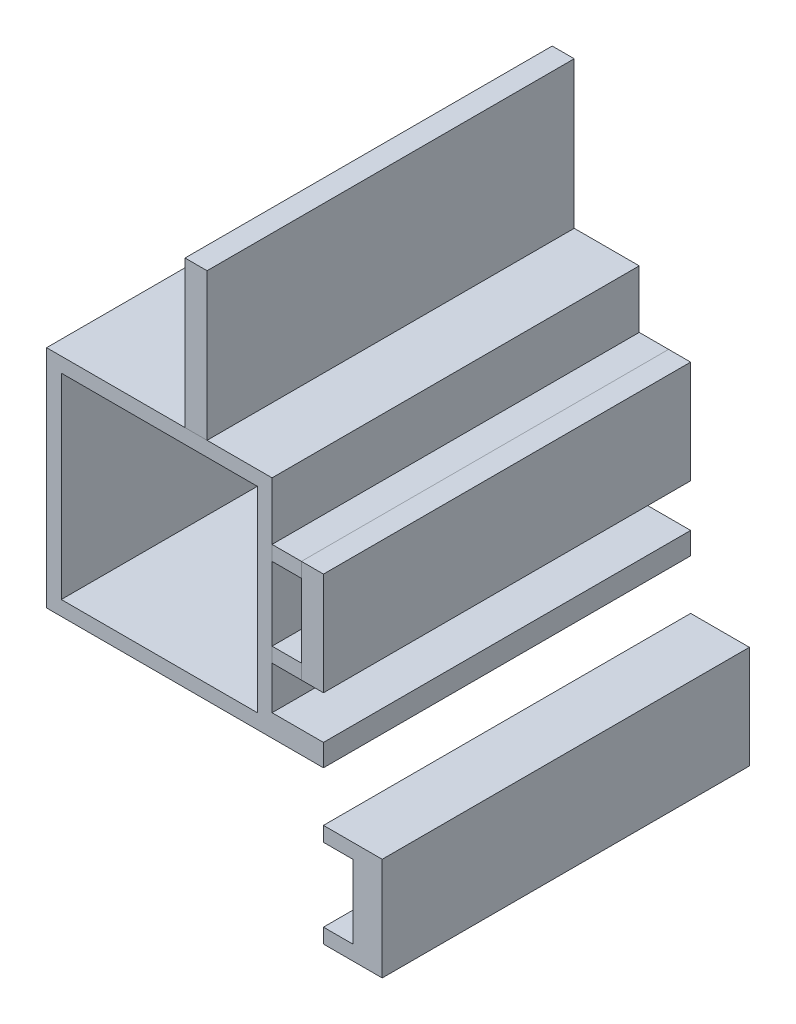
SolidWorks part; units mm, degrees
ref_plane "Alzado" through (0, 0, 0) normal (0, 0, 1) x (1, 0, 0)
ref_plane "Planta" through (0, 0, 0) normal (0, 1, 0) x (1, 0, 0)
ref_plane "Vista lateral" through (0, 0, 0) normal (1, 0, 0) x (0, 0, -1)
sketch "Croquis2" plane through (0, 0, 0) normal (0, 0, 1) x (1, 0, 0)
  line L0 (-51.9511, -1.694) -> (-49.9511, -1.694)
  line L1 (-49.9511, -1.694) -> (-51.9511, -1.694)
  line L2 (-1.9511, -10.694) -> (-1.9511, -41.694)
  line L3 (-1.9511, -41.694) -> (-51.9511, -41.694) construction
  line L4 (-51.9511, -1.694) -> (-51.9511, -41.694) construction
  line L5 (-49.9511, -1.694) -> (-49.9511, -11.294)
  line L6 (-49.9511, -11.294) -> (-36.9511, -11.294)
  line L7 (-36.9511, -11.294) -> (-36.9511, -9.294)
  line L8 (-36.9511, -9.294) -> (-31.9511, -9.294)
  line L9 (-31.9511, -9.294) -> (-31.9511, -11.994)
  line L10 (-31.9511, -11.994) -> (-17.3111, -11.994)
  line L11 (-17.3111, -11.994) -> (-17.3111, -7.694)
  line L12 (-17.3111, -7.694) -> (-24.3111, -7.694)
  line L13 (-24.3111, -7.694) -> (-24.3111, -4.694)
  line L14 (-24.3111, -4.694) -> (-14.3111, -4.694)
  line L15 (-14.3111, -4.694) -> (-14.3111, -10.694)
  line L16 (-14.3111, -10.694) -> (-1.9511, -10.694)
  line L17 (-1.9511, -41.694) -> (-4.5642, -41.694)
  line L18 (-4.5642, -41.694) -> (-4.5642, -19.454)
  line L19 (-4.5642, -19.454) -> (-22.3242, -19.454) construction
  line L20 (-22.3242, -41.694) -> (-22.3242, -15.394) construction
  line L21 (-4.5642, -19.454) -> (-22.3242, -15.394)
  line L22 (-42.1842, -30.694) -> (-40.1642, -30.694)
  line L23 (-22.3242, -15.394) -> (-26.7442, -15.394) construction
  line L24 (-42.1842, -41.694) -> (-42.1842, -30.694) construction
  line L25 (-40.1642, -41.694) -> (-40.1642, -30.694) construction
  line L26 (-26.7442, -15.394) -> (-26.7442, -15.354)
  line L27 (-22.3242, -15.394) -> (-26.7442, -15.354)
  line L28 (-40.1642, -30.694) -> (-26.7442, -15.354) construction
  arc A0 (-40.1642, -30.694) -> (-26.7442, -15.354) centre (-26.4173, -29.1801) cw
  dimension "D1" = 2
  dimension "D2" = 50
  dimension "D3" = 40
  dimension "D4" = 9.6
  dimension "D5" = 13
  dimension "D6" = 2
  dimension "D7" = 5
  dimension "D8" = 2.7
  dimension "D9" = 14.64
  dimension "D10" = 4.3
  dimension "D11" = 3
  dimension "D12" = 10
  dimension "D13" = 6
  dimension "D14" = 12.36
  dimension "D15" = 22.24
  dimension "D16" = 17.76
  dimension "D17" = 26.3
  dimension "D18" = 35.6
  dimension "D19" = 2.02
  dimension "D20" = 11
  dimension "D21" = 4.42
  dimension "D22" = 0.04
sketch "Croquis3" plane through (0, 0, 0) normal (0, 0, 1) x (1, 0, 0)
  line L114 (-15.1572, 8.4809) -> (-41.8572, 8.4809)
  line L133 (-13.1572, 9.4809) -> (-13.1572, 35.1809)
  line L147 (-27.0072, 35.1809) -> (-27.0072, 37.1809) construction
  line L167 (-43.8572, 37.1809) -> (-27.0072, 37.1809)
  line L182 (-15.1572, 35.1809) -> (-41.8572, 35.1809)
  line L183 (-41.8572, 8.4809) -> (-41.8572, 35.1809)
  line L184 (-15.1572, 8.4809) -> (-15.1572, 35.1809)
  line L190 (-43.8572, 37.1809) -> (-43.8572, 6.4809)
  line L192 (-13.1572, 35.1809) -> (-9.1572, 35.1809)
  line L193 (-9.1572, 35.1809) -> (-9.1572, 9.4809)
  line L194 (-9.1572, 9.4809) -> (-13.1572, 9.4809)
  line L195 (-9.1572, 22.3309) -> (-6.1572, 22.3309) construction
  line L196 (-27.0072, 37.1809) -> (-6.1572, 37.1809)
  line L202 (-43.8572, 6.4809) -> (-6.1572, 6.4809)
  line L214 (-6.1572, 6.4809) -> (-6.1572, 37.1809)
  dimension "D5" = 26.7
  dimension "D13" = 3
  dimension "D3" = 2
  dimension "D10" = 37.7
  dimension "D4" = 26.7
  dimension "D8" = 4
  dimension "D12" = 2
  dimension "D28" = 16.85
extrude "Saliente-Extruir1" add sketch "Croquis3" along normal blind 50 contours L196 L214 L202 L190 L167 | L183 L182 L184 L114 | L194 L133 L192 L193
sketch "Croquis11" plane through (0, 0, 0) normal (0, 0, -1) x (-1, 0, 0)
  line L2 (-1.8428, -14.3028) -> (-1.8428, -0.3028)
  line L3 (-1.8428, -0.3028) -> (6.1572, -0.3028)
  line L4 (6.1572, -0.3028) -> (6.1572, -2.3028)
  line L5 (6.1572, -2.3028) -> (2.1572, -2.3028)
  line L6 (2.1572, -2.3028) -> (2.1572, -12.3028)
  line L7 (2.1572, -12.3028) -> (6.1572, -12.3028)
  line L8 (6.1572, -12.3028) -> (6.1572, -14.3028)
  line L9 (-1.8428, -14.3028) -> (6.1572, -14.3028)
  line L14 (2.1572, -7.3028) -> (3.8938, -7.3028) construction
  dimension "D1" = 8
  dimension "D2" = 2
  dimension "D3" = 2
  dimension "D4" = 14
  dimension "D5" = 4
extrude "Saliente-Extruir2" add sketch "Croquis11" along direction (0, 0, 1) on the side against the normal up to surface (50 mm away) contours L9 L8 L7 L6 L5 L4 L3 L2 up to face at (-11.1572, 22.3309, 50)
sketch "Croquis12" plane through (1.8428, 0, 0) normal (1, 0, 0) x (0, 0, -1)
  line L0 (-45.4229, -7.3028) -> (-43.4878, -7.3028) construction
  line L2 (0, -7.3028) -> (-1.743, -7.3028) construction
  line L4 (0, -0.3028) -> (0, -14.3028) construction
  line L5 (-25, -9.8028) -> (-4.8, -9.8028)
  line L8 (-4.8, -4.8028) -> (-45.4229, -4.8028)
  line L9 (-45.4229, -4.8028) -> (-45.4229, -9.8028)
  line L10 (-45.4229, -9.8028) -> (-25, -9.8028)
  line L11 (-4.8, -9.8028) -> (-4.8, -4.8028)
  dimension "D3" = 5
extrude "Cortar-Extruir12" cut sketch "Croquis12" against normal up to surface (10 mm away) contours L11 L8 L9 L10 L5 rebuild error yes
fillet "Redondeo1" radius 2.5 rebuild error yes
sketch "Croquis14" plane through (-6.1572, 0, 0) normal (1, 0, 0) x (0, 0, -1)
  line L1 (-50, 9.4809) -> (-50, 35.1809) construction
  line L2 (-50, 22.3309) -> (-47.0206, 22.3309) construction
  line L3 (-25, 37.1809) -> (-25, 24.8309) construction
  line L6 (-47.0206, 22.3309) -> (-47.0206, 24.8309)
  line L7 (-47.0206, 24.8309) -> (-2.9794, 24.8309)
  line L8 (-47.0206, 22.3309) -> (-47.0206, 19.8309)
  line L9 (-47.0206, 19.8309) -> (-2.9794, 19.8309)
  line L10 (-2.9794, 22.3309) -> (-2.9794, 19.8309)
  line L11 (-2.9794, 22.3309) -> (-2.9794, 24.8309)
  point P12 (-25, 19.8309)
  dimension "D1" = 2.5
  dimension "D2" = 2.5
extrude "Cortar-Extruir14" cut sketch "Croquis14" against normal up to surface (9 mm away) contours L10 L11 L7 L6 L8 L9 rebuild error yes up to face at (-15.1572, 21.8309, 25)
fillet "Redondeo2" radius 2.5 rebuild error yes
fillet "Redondeo4" radius 2.5 rebuild error yes
ref_plane "Plano1" through (-48.1572, 0, 0) normal (-1, 0, 0) x (0, 0, 1)
sketch "Croquis16" plane through (-48.1572, 0, 0) normal (-1, 0, 0) x (0, 0, 1)
  line L0 (32, -25.4812) -> (18, -25.4812)
  line L2 (25, 5.245) -> (25, 1.245) construction
  line L3 (50, 5.245) -> (0, 5.245) construction
  line L9 (5, -11.755) -> (5, -12.4812)
  line L10 (32, 1.245) -> (18, 1.245)
  line L11 (45, -12.4812) -> (45, -11.755)
  line L16 (5, -12.1181) -> (45, -12.1181) construction
  arc A0 (32, 1.245) -> (45, -11.755) centre (32, -11.755) cw
  arc A3 (5, -11.755) -> (18, 1.245) centre (18, -11.755) cw
  arc A4 (32, -25.4812) -> (45, -12.4812) centre (32, -12.4812) ccw
  arc A5 (5, -12.4812) -> (18, -25.4812) centre (18, -12.4812) ccw
  point P0 (25, 5.245)
  dimension "D2" = 7
  dimension "D1" = 4
extrude "Cortar-Extruir17" cut sketch "Croquis16" against normal up to surface (16.5053 mm away) rebuild error yes
sketch "Croquis17" plane through (-43.8572, 0, 0) normal (-1, 0, 0) x (0, 0, 1)
  line L0 (25, 32.1809) -> (25, 37.1809) construction
  line L1 (3, 12.4809) -> (47, 12.4809)
  line L2 (3, 12.4809) -> (3, 32.1809)
  line L3 (3, 32.1809) -> (47, 32.1809)
  line L4 (47, 12.4809) -> (47, 32.1809)
  line L5 (50, 37.1809) -> (0, 37.1809) construction
  line L6 (47, 22.3309) -> (50, 22.3309) construction
  line L7 (50, 37.1809) -> (50, 6.4809) construction
  line L8 (3, 22.3309) -> (0, 22.3309) construction
  line L9 (0, 37.1809) -> (0, 6.4809) construction
  line L12 (50, 7.4809) -> (0, 7.4809) construction
  dimension "D1" = 3
  dimension "D2" = 3
  dimension "D3" = 5
  dimension "D4" = 5
extrude "Cortar-Extruir18" cut sketch "Croquis17" against normal up to next contours L1 L4 L3 L2 rebuild error yes
fillet "Redondeo5" radius 10 rebuild error yes
sketch "Croquis18" plane through (0, 37.1809, 0) normal (0, 1, 0) x (1, 0, 0)
  line L0 (-28.5072, -4) -> (-28.5072, 0) construction
  line L1 (-25.0072, -46) -> (-32.0072, -46)
  line L2 (-25.0072, -46) -> (-25.0072, -4)
  line L3 (-25.0072, -4) -> (-32.0072, -4)
  line L4 (-15.1572, 0) -> (-41.8572, 0)
  line L5 (-15.1572, -50) -> (-15.1572, 0)
  line L6 (-41.8572, -50) -> (-15.1572, -50)
  line L7 (-41.8572, 0) -> (-41.8572, -50)
  line L8 (-15.1572, 0) -> (-41.8572, 0) construction
  line L9 (-15.1572, -50) -> (-15.1572, 0) construction
  line L10 (-41.8572, -50) -> (-15.1572, -50) construction
  line L11 (-41.8572, 0) -> (-41.8572, -50) construction
  line L12 (-32.0072, -46) -> (-32.0072, -4)
  point P8 (-28.5072, -4)
  point P9 (-28.5072, 0)
  dimension "D2" = 4
  dimension "D3" = 4
  dimension "D4" = 7
  dimension "D1" = 0
extrude "Cortar-Extruir19" cut sketch "Croquis18" against normal up to next rebuild error yes
sketch "Croquis19" plane through (0, 0, 0) normal (0, 0, -1) x (-1, 0, 0)
  line L0 (9.1572, 35.1809) -> (9.1572, 9.4809) construction
  line L1 (9.1572, 17.3309) -> (13.1572, 17.3309)
  line L2 (9.1572, 17.3309) -> (9.1572, 15.3309)
  line L3 (9.1572, 15.3309) -> (13.1572, 15.3309)
  line L4 (13.1572, 17.3309) -> (13.1572, 15.3309)
  line L5 (13.1572, 9.4809) -> (13.1572, 35.1809) construction
  line L6 (9.1572, 17.3309) -> (9.1572, 22.3309) construction
  line L7 (9.1572, 22.3309) -> (7.709, 22.3309) construction
  line L8 (13.1572, 27.3309) -> (13.1572, 29.3309)
  line L9 (9.1572, 29.3309) -> (13.1572, 29.3309)
  line L10 (9.1572, 27.3309) -> (9.1572, 29.3309)
  line L11 (9.1572, 27.3309) -> (13.1572, 27.3309)
  line L12 (25.0072, 37.1809) -> (32.0072, 37.1809) construction
  line L13 (25.0072, 37.1809) -> (32.0072, 37.1809) construction
  line L15 (25.0072, 37.1809) -> (22.0072, 37.1809)
  line L16 (25.0072, 37.1809) -> (25.0072, 57.1809)
  line L17 (25.0072, 57.1809) -> (22.0072, 57.1809)
  line L18 (22.0072, 37.1809) -> (22.0072, 57.1809)
  dimension "D1" = 2
  dimension "D2" = 5
  dimension "D3" = 3
  dimension "D4" = 20
extrude "Saliente-Extruir3" add sketch "Croquis19" against normal up to surface (50 mm away) up to face at (-11.1572, 22.3309, 50)
sketch "Croquis20" plane through (-25.0072, 0, 0) normal (-1, 0, 0) x (0, 0, 1)
  line L0 (0, 46.1809) -> (20.5, 46.1809) construction
  line L1 (0, 37.1809) -> (0, 57.1809) construction
  line L2 (20.5, 46.1809) -> (30, 46.1809) construction
  line L3 (30, 46.1809) -> (30, 37.1809) construction
  line L4 (25.25, 46.1809) -> (25.25, 35.1809) construction
  line L5 (3, 44.3809) -> (3, 47.9809)
  line L6 (3, 47.9809) -> (47, 47.9809)
  line L7 (47, 47.9809) -> (47, 44.3809)
  line L8 (50, 57.1809) -> (50, 37.1809) construction
  line L9 (3, 44.3809) -> (47, 44.3809)
  line L10 (30, 37.1809) -> (4, 37.1809) construction
  line L11 (47, 47.9809) -> (47, 50.9809) construction
  line L14 (47, 44.3809) -> (47, 37.1809) construction
  line L15 (46, 35.1809) -> (4, 35.1809) construction
  point P15 (47, 46.1809)
  point P16 (3, 46.1809)
  dimension "D1" = 20.5
  dimension "D2" = 9.5
  dimension "D3" = 3
  dimension "D4" = 3
  dimension "D5" = 3
  dimension "D6" = 1.8
  dimension "D7" = 11
extrude "Cortar-Extruir20" cut sketch "Croquis20" against normal up to next rebuild error yes
sketch "Croquis21" plane through (0, 0, 0) normal (0, 0, -1) x (-1, 0, 0)
  line L0 (13.1572, 35.1809) -> (13.1572, 37.1809)
  line L1 (43.8572, 37.1809) -> (6.1572, 37.1809) construction
  line L2 (13.1572, 37.1809) -> (6.1572, 37.1809)
  line L3 (6.1572, 37.1809) -> (6.1572, 29.3309)
  line L4 (6.1572, 37.1809) -> (6.1572, -0.3028) construction
  line L5 (6.1572, 29.3309) -> (9.1572, 29.3309)
  line L6 (9.1572, 29.3309) -> (9.1572, 35.1809)
  line L7 (9.1572, 35.1809) -> (13.1572, 35.1809)
  line L8 (9.1572, 9.4809) -> (6.1572, 9.4809)
  line L9 (6.1572, 9.4809) -> (6.1572, 15.3309)
  line L10 (6.1572, 15.3309) -> (9.1572, 15.3309)
  line L11 (9.1572, 15.3309) -> (9.1572, 9.4809)
extrude "Cortar-Extruir21" cut sketch "Croquis21" against normal up to next (50 mm away)
fillet "Redondeo6" radius 3 rebuild error yes
fillet "Redondeo8" radius 7 rebuild error yes
fillet "Redondeo9" radius 1.3 rebuild error yes
sketch "Croquis22" plane through (0, 37.1809, 0) normal (0, 1, 0) x (1, 0, 0)
  line L5 (-32.0072, -46) -> (-25.0072, -46) construction
  line L6 (-32.0072, -4) -> (-39.0072, -4)
  line L7 (-32.0072, -4) -> (-32.0072, -46)
  line L8 (-32.0072, -46) -> (-39.0072, -46)
  line L9 (-39.0072, -4) -> (-39.0072, -46)
  dimension "D1" = 7
extrude "Cortar-Extruir22" cut sketch "Croquis22" against normal up to next rebuild error yes
fillet "Redondeo10" radius 6.5 rebuild error yes
